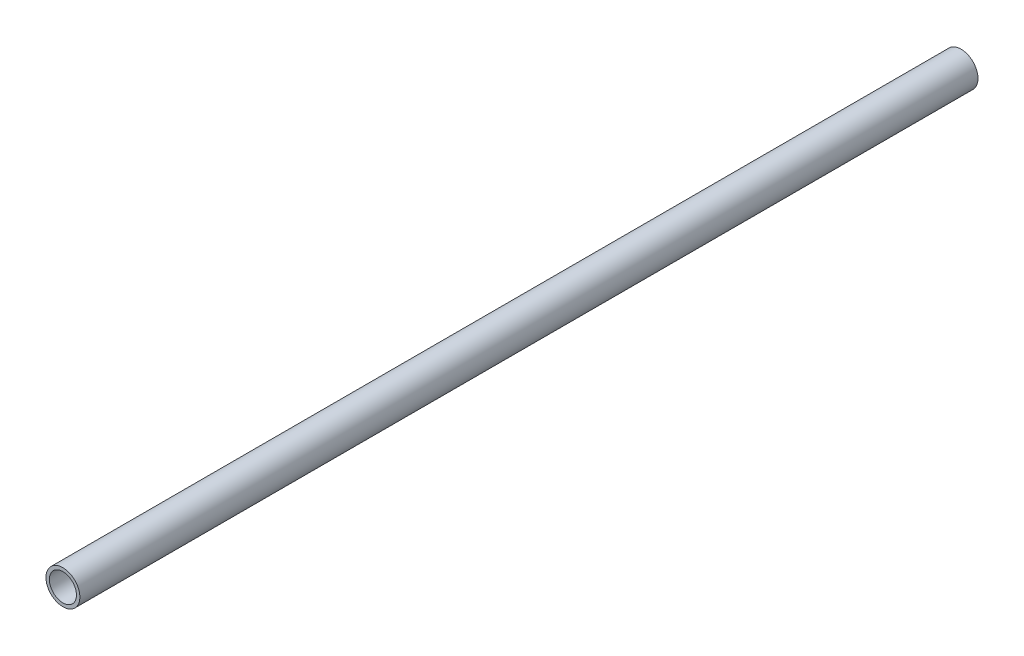
SolidWorks part; units mm, degrees
ref_plane "Piano frontale" through (0, 0, 0) normal (0, 0, 1) x (1, 0, 0)
ref_plane "Piano superiore" through (0, 0, 0) normal (0, 1, 0) x (1, 0, 0)
ref_plane "Piano destro" through (0, 0, 0) normal (1, 0, 0) x (0, 0, -1)
sketch "Schizzo1" plane through (0, 0, 0) normal (0, 0, 1) x (1, 0, 0)
  circle A0 centre (0, 0) radius 10
  circle A1 centre (0, 0) radius 8
  dimension "D1" = 20
  dimension "D2" = 2
extrude "Estrusione-Estrusione1" add sketch "Schizzo1" along normal blind 530
